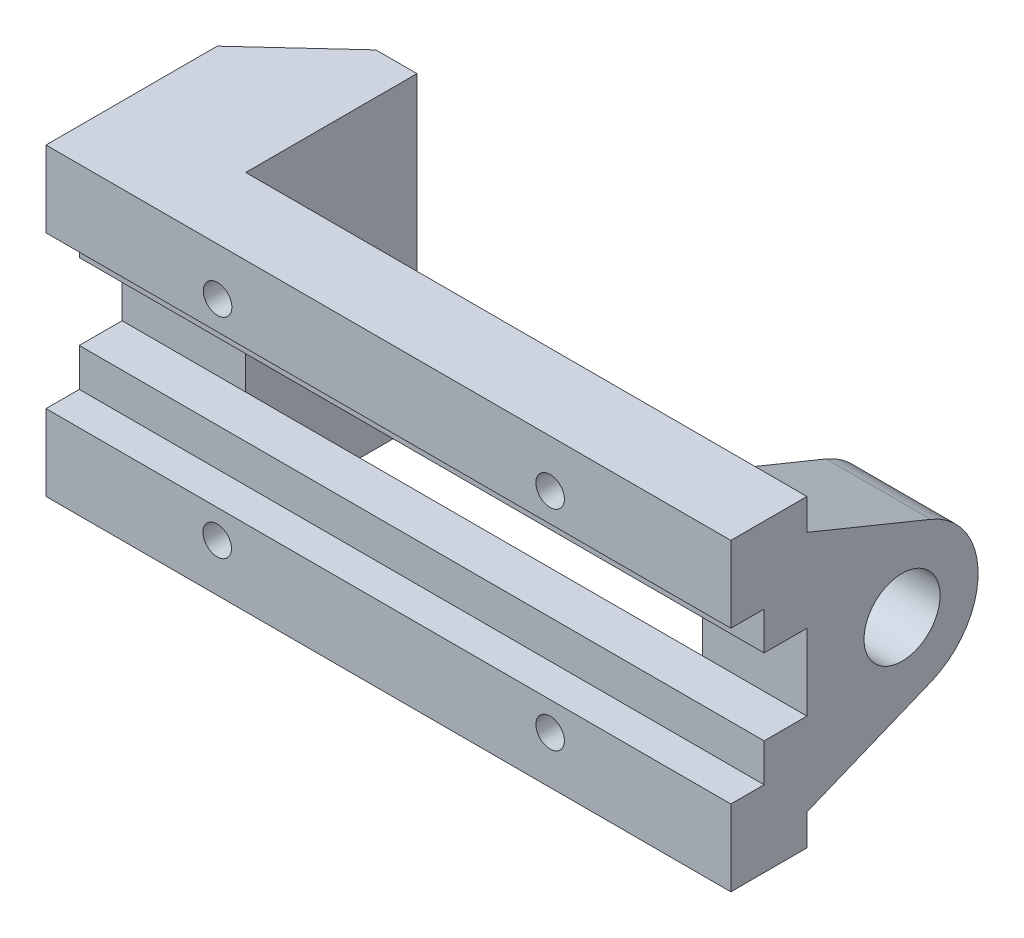
SolidWorks part; units mm, degrees
ref_plane "Front Plane" through (0, 0, 0) normal (0, 0, 1) x (1, 0, 0)
ref_plane "Top Plane" through (0, 0, 0) normal (0, 1, 0) x (1, 0, 0)
ref_plane "Right Plane" through (0, 0, 0) normal (1, 0, 0) x (0, 0, -1)
sketch "Sketch3" plane through (0, 0, 0) normal (0, 1, 0) x (1, 0, 0)
  line L10 (26, 36) -> (26, 0)
  line L13 (0, 0) -> (0, 20)
  line L14 (17.3622, 36) -> (26, 36)
  line L15 (0, 0) -> (0, -16)
  line L16 (0, -16) -> (144, -16)
  line L17 (144, 0) -> (144, -16)
  line L18 (17.3622, 36) -> (0, 20)
  line L19 (26, 0) -> (144, 0)
  dimension "D1" = 144
  dimension "D2" = 36
  dimension "D3" = 16
  dimension "D4" = 16
extrude "Boss-Extrude2" add sketch "Sketch3" along normal blind 64
sketch "Sketch8" plane through (144, 0, 0) normal (1, 0, 0) x (0, 0, -1)
  line L0 (0, 40) -> (0, 24)
  line L1 (36, 64) -> (36, 0) construction
  line L2 (-16, 32) -> (58.7531, 32) construction
  line L3 (-16, 64) -> (26.0538, 46.8105)
  line L4 (-16, 0) -> (26.0538, 17.1895)
  line L7 (0, 64) -> (0, 0) construction
  line L8 (-16, 64) -> (-16, 0) construction
  line L11 (0, 64) -> (0, 0) construction
  line L12 (-16, 32) -> (-16, 48)
  line L13 (-16, 32) -> (-16, 16)
  line L14 (-16, 16) -> (-16, 0)
  line L15 (-16, 48) -> (-16, 64)
  line L16 (-16, 48) -> (-9, 48)
  line L17 (-9, 48) -> (-9, 40)
  line L18 (-9, 40) -> (0, 40)
  line L19 (0, 24) -> (-9, 24)
  line L20 (-16, 16) -> (-9, 16)
  line L21 (-9, 16) -> (-9, 24)
  circle A0 centre (20, 32) radius 8
  arc A1 (26.0538, 17.1895) -> (26.0538, 46.8105) centre (20, 32) ccw
  dimension "D1" = 16
  dimension "D2" = 32
  dimension "D3" = 32
  dimension "D4" = 16
  dimension "D5" = 7
extrude "Boss-Extrude3" add sketch "Sketch8" against normal blind 22 contours L2 L7 L4 A1 A0 | L0 L2 A0 A1 L3 L7 | L17 L18 L7 L3 L11 L16 | L21 L20 L11 L4 L7 L19 region at (144, 42.7243, -14.0117) region at (144, 51.7614, 7.592) region at (144, 21.2757, -14.0117) region at (144, 12.2386, 7.592)
extrude "Cut-Extrude1" cut sketch "Sketch8<6>" against normal through all and the other way through all contours L11 L2 L0 L18 L17 L16 | L2 L11 L20 L21 L19 L7 region at (144, 38.4348, 9.3696) region at (144, 25.5652, 9.3696)
sketch "Sketch8<6>" plane through (144, 0, 0) normal (1, 0, 0) x (0, 0, -1) same geometry as "Sketch8"
sketch "Sketch9" plane through (0, 0, 16) normal (0, 0, 1) x (1, 0, 0)
  line L0 (144, 64) -> (106, 64)
  line L1 (0, 64) -> (144, 64) construction
  line L3 (144, 0) -> (106, 0)
  line L4 (0, 0) -> (144, 0) construction
  circle A0 centre (106, 54) radius 3
  circle A1 centre (106, 10) radius 3
  circle A2 centre (36.0806, 54) radius 3
  circle A3 centre (36, 10) radius 3
  point P18 (0, 0)
  point P19 (0, 0)
  point P20 (0, 0)
extrude "Cut-Extrude2" cut sketch "Sketch9" against normal blind 11 contours A0 | A3 | A1 | A2 region at (106, 54, 16) region at (106, 10, 16) region at (36, 10, 16)
